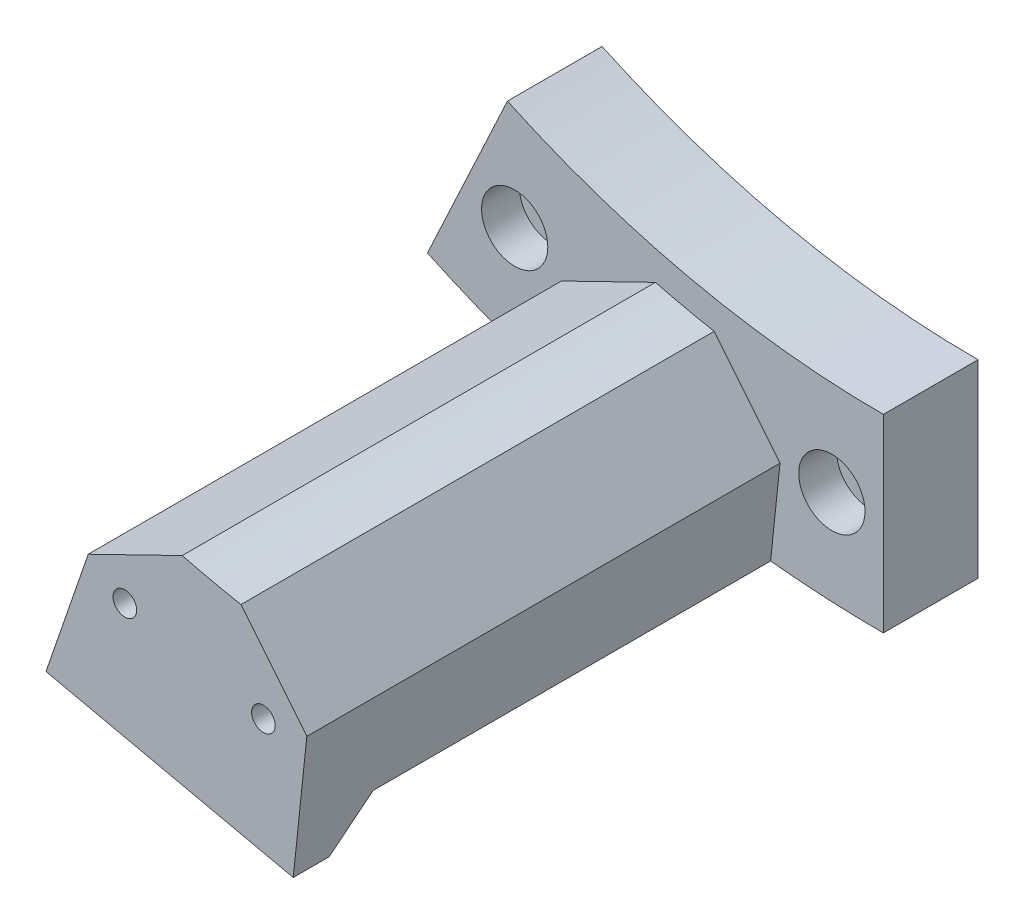
SolidWorks part; units mm, degrees
ref_plane "Plan de face" through (0, 0, 0) normal (0, 0, 1) x (1, 0, 0)
ref_plane "Plan de dessus" through (0, 0, 0) normal (0, 1, 0) x (1, 0, 0)
ref_plane "Plan de droite" through (0, 0, 0) normal (1, 0, 0) x (0, 0, -1)
sketch "Esquisse1" plane through (0, 0, 0) normal (0, 0, 1) x (1, 0, 0)
  line L0 (0, 0) -> (0, -114) construction
  line L1 (0, 0) -> (-48.1785, -103.3191) construction
  line L2 (-39.7261, -85.1929) -> (-48.1785, -103.3191)
  line L3 (0, -94) -> (0, -114)
  arc A0 (0, -114) -> (-48.1785, -103.3191) centre (0, 0) cw
  arc A1 (0, -94) -> (-39.7261, -85.1929) centre (0, 0) cw
  dimension "D2" = 114
  dimension "D3" = 94
  dimension "D1" = 25
extrude "Boss.-Extru.1" add sketch "Esquisse1" along normal blind 10
sketch "Esquisse2" plane through (0, 0, 10) normal (0, 0, 1) x (1, 0, 0)
  line L0 (0, 0) -> (-24.6741, -111.2977) construction
  line L1 (0, 0) -> (-11.9162, -113.3755) construction
  line L2 (0, 0) -> (-37.1148, -107.7891) construction
  line L3 (-31.5801, -91.7153) -> (-37.1148, -107.7891)
  line L4 (-10.1393, -96.4686) -> (-11.9162, -113.3755)
  arc A0 (-48.1785, -103.3191) -> (0, -114) centre (0, 0) ccw construction
  arc A1 (-11.9162, -113.3755) -> (-37.1148, -107.7891) centre (0, 0) cw
  arc A2 (-10.1393, -96.4686) -> (-31.5801, -91.7153) centre (0, 0) cw
  arc A3 (-39.7261, -85.1929) -> (0, -94) centre (0, 0) ccw construction
  point P10 (-24.6741, -111.2977)
  dimension "D1" = 3
  dimension "D2" = 13
extrude "Boss.-Extru.2" add sketch "Esquisse2" along normal blind 48
sketch "Esquisse4" plane through (0, 0, 58) normal (0, 0, 1) x (1, 0, 0)
  line L0 (-38.4854, -111.7696) -> (-12.3563, -117.5623)
  line L1 (-12.3563, -117.5623) -> (-10.1393, -96.4686)
  line L2 (-31.5801, -91.7153) -> (-38.4854, -111.7696)
  line L3 (-31.5801, -91.7153) -> (-37.1148, -107.7891) construction
  line L4 (-11.9162, -113.3755) -> (-10.1393, -96.4686) construction
  arc A0 (-31.5801, -91.7153) -> (-10.1393, -96.4686) centre (0, 0) ccw construction
  arc A1 (-31.5801, -91.7153) -> (-10.1393, -96.4686) centre (0, 0) ccw
  arc A2 (-37.1148, -107.7891) -> (-11.9162, -113.3755) centre (0, 0) ccw construction
  point P14 (-24.6741, -111.2977)
  dimension "D1" = 3.45
extrude "Boss.-Extru.3" add sketch "Esquisse4" along normal blind 2
chamfer "Chanfrein1" distance 6 angle 45 1 edges at (-24.6741, -111.2977, 58)
sketch "Esquisse5" plane through (0, 0, 10) normal (0, 0, 1) x (1, 0, 0)
  line L0 (0, 0) -> (-42.7052, -105.699) construction
  line L1 (0, 0) -> (-5.9663, -113.8438) construction
  line L2 (-42.7052, -105.699) -> (-35.213, -87.1553) construction
  line L3 (0, -114) -> (0, -94) construction
  line L4 (-39.7261, -85.1929) -> (-48.1785, -103.3191) construction
  arc A0 (-48.1785, -103.3191) -> (-37.1148, -107.7891) centre (0, 0) ccw construction
  arc A1 (-11.9162, -113.3755) -> (0, -114) centre (0, 0) ccw construction
  arc A2 (-39.7261, -85.1929) -> (0, -94) centre (0, 0) ccw construction
  arc A3 (0, -104) -> (-43.9523, -94.256) centre (0, 0) cw construction
  circle A4 centre (-5.4429, -103.8575) radius 1.75
  circle A5 centre (-38.9591, -96.4271) radius 1.75
  point P20 (-38.9591, -96.4271)
  dimension "D1" = 3.5
extrude "Enlèv. mat.-Extru.1" cut sketch "Esquisse5" against normal up to next
sketch "Esquisse6" plane through (0, 0, 10) normal (0, 0, 1) x (1, 0, 0)
  circle A0 centre (-38.9591, -96.4271) radius 3.5
  circle A1 centre (-5.4429, -103.8575) radius 3.5
  dimension "D1" = 7
extrude "Enlèv. mat.-Extru.2" cut sketch "Esquisse6" against normal blind 4
chamfer "Chanfrein2" distance 7.5 angle 45 2 edges at (-10.1393, -96.4686, 35) (-31.5801, -91.7153, 35)
sketch "Esquisse7" plane through (0, 0, 60) normal (0, 0, 1) x (1, 0, 0)
  line L0 (-20.9946, -94.7007) -> (-24.6741, -111.2977) construction
  line L1 (-30.1566, -101.3759) -> (-15.5122, -104.6225) construction
  arc A0 (-37.1148, -107.7891) -> (-11.9162, -113.3755) centre (0, 0) ccw construction
  arc A1 (-37.1148, -107.7891) -> (-11.9162, -113.3755) centre (0, 0) ccw construction
  arc A2 (-24.0879, -93.9616) -> (-17.8788, -95.3381) centre (0, 0) ccw construction
  circle A3 centre (-30.1566, -101.3759) radius 1.25
  circle A4 centre (-15.5122, -104.6225) radius 1.25
  point P12 (-22.8344, -102.9992)
  point P13 (-22.8344, -102.9992)
  dimension "D1" = 2.5
  dimension "D2" = 15
extrude "Enlèv. mat.-Extru.3" cut sketch "Esquisse7" against normal blind 10
